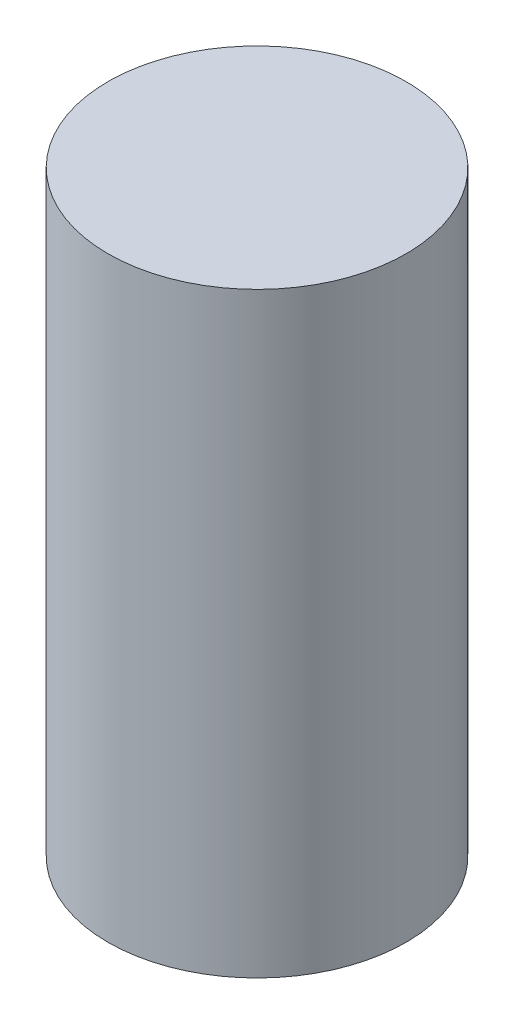
SolidWorks part; units mm, degrees
ref_plane "Front Plane" through (0, 0, 0) normal (0, 0, 1) x (1, 0, 0)
ref_plane "Top Plane" through (0, 0, 0) normal (0, 1, 0) x (1, 0, 0)
ref_plane "Right Plane" through (0, 0, 0) normal (1, 0, 0) x (0, 0, -1)
sketch "Sketch2" plane through (0, 0, 0) normal (0, 1, 0) x (1, 0, 0)
  circle A0 centre (0, 0) radius 1.5875
  dimension "D1" = 3.175
extrude "Boss-Extrude1" add sketch "Sketch2" along normal blind 6.35
